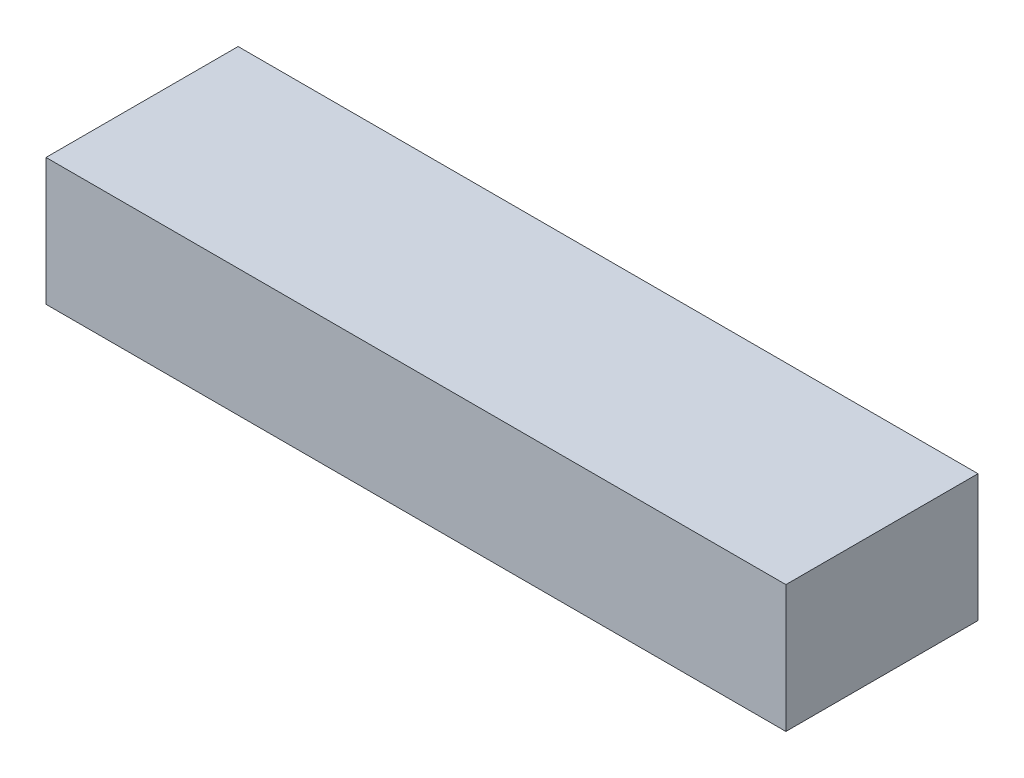
SolidWorks part; units mm, degrees
ref_plane "Front Plane" through (0, 0, 0) normal (0, 0, 1) x (1, 0, 0)
ref_plane "Top Plane" through (0, 0, 0) normal (0, 1, 0) x (1, 0, 0)
ref_plane "Right Plane" through (0, 0, 0) normal (1, 0, 0) x (0, 0, -1)
sketch "Sketch1" plane through (0, 0, 0) normal (0, 1, 0) x (1, 0, 0)
  line L1 (570, -148) -> (-570, -148)
  line L2 (570, -148) -> (570, 148)
  line L3 (570, 148) -> (-570, 148)
  line L4 (-570, -148) -> (-570, 148)
  line L5 (570, -148) -> (-570, 148) construction
  line L6 (570, 148) -> (-570, -148) construction
  point P0 (0, 0)
  dimension "D1" = 1140
  dimension "D2" = 296
extrude "Boss-Extrude1" add sketch "Sketch1" along normal blind 196
equation "\"assembly\"= 0"
equation "\"thickness 1\" = 2"
equation "\"thickness 2\" = 3"
equation "\"connecting flange\" = 35"
equation "\"main\"= 0"
equation "\"main length\" = 1200"
equation "\"main width\" = 1200"
equation "\"divider panel distance offset\" = 296"
equation "\"side panel\"= 0"
equation "\"access hatch length\" = 600"
equation "\"access hatch width\" = 450"
equation "\"access hatch offset X\" = 100"
equation "\"access hatch offset Y\" = 100"
equation "\"side panel length\" = 1200"
equation "\"side panel width\" = 950"
equation "\"back panel\"= 0"
equation "\"back panel access hatch length\" = 1150"
equation "\"back panel access hatch width\" = 206"
equation "\"back panel access hatch flange\" = 40"
equation "\"drift eliminator\"= 0"
equation "\"drift eliminator size offset\" = 10"
equation "\"drift eliminator length\" = \"back panel access hatch length\" - \"drift eliminator size offset\""
equation "\"drift eliminator width\" = \"back panel access hatch width\" - \"drift eliminator size offset\""
equation "\"drift eliminator depth\" = \"divider panel distance offset\""
equation "\"sump\"= 0"
equation "\"D1@Boss-Extrude1\"=\"drift eliminator width\""
equation "\"D1@Sketch1\"=\"drift eliminator length\""
equation "\"D2@Sketch1\"=\"drift eliminator depth\""
